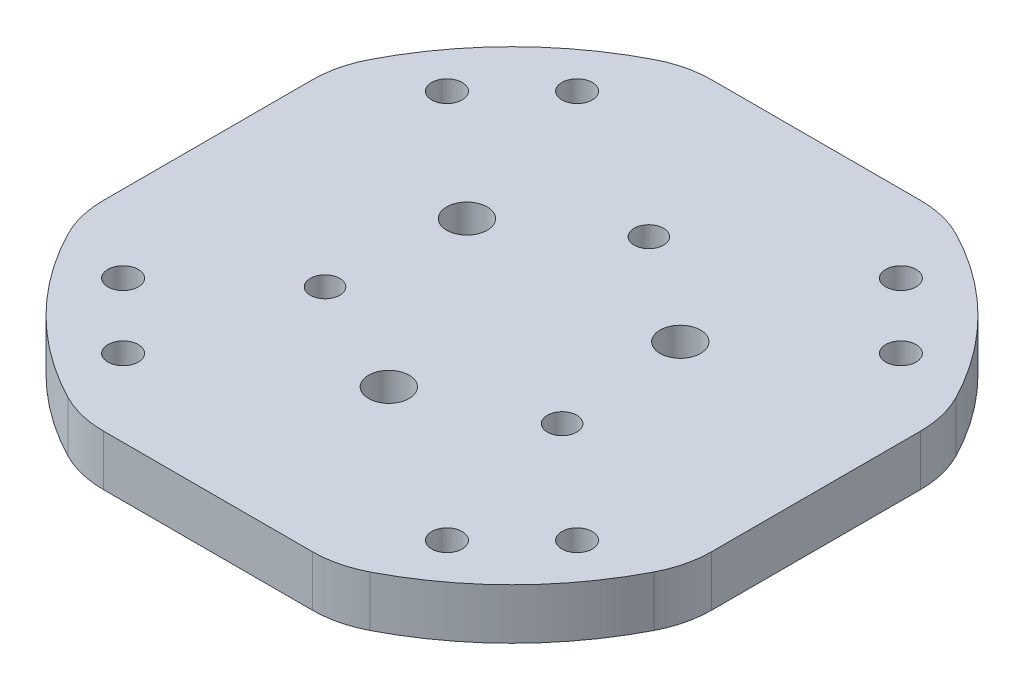
SolidWorks part; units mm, degrees
ref_plane "前视基准面" through (0, 0, 0) normal (0, 0, 1) x (1, 0, 0)
ref_plane "上视基准面" through (0, 0, 0) normal (0, 1, 0) x (1, 0, 0)
ref_plane "右视基准面" through (0, 0, 0) normal (1, 0, 0) x (0, 0, -1)
sketch "草图1" plane through (0, 0, 0) normal (0, 1, 0) x (1, 0, 0)
  line L0 (0, 0) -> (0, 33.3478) construction
  line L1 (0, 0) -> (11.2563, 0) construction
  line L2 (-11.6913, -6.75) -> (0, 0) construction
  line L3 (0, 0) -> (11.6913, -6.75) construction
  line L4 (0, 0) -> (-10.5222, 6.075) construction
  line L5 (10.5222, 6.075) -> (0, 0) construction
  circle A0 centre (0, 0) radius 19
  circle A1 centre (0, 13.5) radius 1.45
  circle A2 centre (0, 0) radius 13.5 construction
  circle A3 centre (-11.6913, -6.75) radius 1.45
  circle A4 centre (11.6913, -6.75) radius 1.45
  circle A5 centre (0, 0) radius 12.15 construction
  circle A6 centre (-10.5222, 6.075) radius 2
  circle A7 centre (0, -12.15) radius 2
  circle A8 centre (10.5222, 6.075) radius 2
  dimension "D1" = 38
  dimension "D2" = 27
  dimension "D3" = 2.9
  dimension "D6" = 24.3
  dimension "D8" = 4
  dimension "D4" = 120
  dimension "D5" = 120
  dimension "D7" = 60
  dimension "D9" = 60
extrude "凸台-拉伸1" add sketch "草图1" along normal blind 12
sketch "草图2" plane through (0, 12, 0) normal (0, 1, 0) x (1, 0, 0)
  line L0 (0, 21.9393) -> (0, 0) construction
  line L1 (0, 21.9393) -> (-19, 10.9697)
  line L2 (-19, 10.9697) -> (-19, -10.9697)
  line L3 (-19, -10.9697) -> (0, -21.9393)
  line L4 (0, -21.9393) -> (19, -10.9697)
  line L5 (19, -10.9697) -> (19, 10.9697)
  line L6 (19, 10.9697) -> (0, 21.9393)
  circle A0 centre (0, 0) radius 19 construction
  circle A1 centre (0, 13.5) radius 1.45
  circle A2 centre (0, 13.5) radius 1.45 construction
  circle A3 centre (-10.5222, 6.075) radius 2
  circle A4 centre (-10.5222, 6.075) radius 2 construction
  circle A5 centre (10.5222, 6.075) radius 2
  circle A6 centre (10.5222, 6.075) radius 2 construction
  circle A7 centre (-11.6913, -6.75) radius 1.45
  circle A8 centre (-11.6913, -6.75) radius 1.45 construction
  circle A9 centre (0, -12.15) radius 2
  circle A10 centre (0, -12.15) radius 2 construction
  circle A11 centre (11.6913, -6.75) radius 1.45
  circle A12 centre (11.6913, -6.75) radius 1.45 construction
  dimension "D1" = 38
extrude "凸台-拉伸2" add sketch "草图2" against normal blind 7
sketch "草图3" plane through (9.5, 0, 16.4545) normal (0.5, 0, 0.866) x (0.866, 0, -0.5)
  line L1 (0, 12) -> (0, 5) construction
  line L2 (-10.9697, 12) -> (10.9697, 12) construction
  circle A1 centre (0, 8.5) radius 1.45
  dimension "D1" = 2.9
extrude "切除-拉伸1" cut sketch "草图3" against normal blind 8
sketch "草图4" plane through (-9.5, 0, 16.4545) normal (-0.5, 0, 0.866) x (0.866, 0, 0.5)
  line L0 (0, 5) -> (0, 12) construction
  line L1 (-10.9697, 12) -> (10.9697, 12) construction
  circle A0 centre (0, 8.5) radius 1.45
  dimension "D1" = 2.9
extrude "切除-拉伸2" cut sketch "草图4" against normal blind 8
sketch "草图5" plane through (-19, 0, 0) normal (-1, 0, 0) x (0, 0, 1)
  line L0 (0, 5) -> (0, 12) construction
  line L1 (-10.9697, 12) -> (10.9697, 12) construction
  circle A0 centre (0, 8.5) radius 1.45
  dimension "D1" = 2.9
extrude "切除-拉伸3" cut sketch "草图5" against normal blind 8
sketch "草图6" plane through (19, 0, 0) normal (1, 0, 0) x (0, 0, -1)
  line L0 (0, 12) -> (0, 5) construction
  line L1 (-10.9697, 12) -> (10.9697, 12) construction
  circle A0 centre (0, 8.5) radius 1.45
  dimension "D1" = 2.9
extrude "切除-拉伸4" cut sketch "草图6" against normal blind 8
sketch "草图7" plane through (9.5, 0, -16.4545) normal (0.5, 0, -0.866) x (-0.866, 0, -0.5)
  line L0 (0, 12) -> (0, 5) construction
  line L1 (-10.9697, 12) -> (10.9697, 12) construction
  circle A0 centre (0, 8.5) radius 1.45
  dimension "D1" = 2.9
extrude "切除-拉伸5" cut sketch "草图7" against normal blind 8
sketch "草图8" plane through (0, 12, 0) normal (0, 1, 0) x (1, 0, 0)
  line L0 (0, 0) -> (0, 38.6602) construction
  line L1 (0, 0) -> (44.9682, 0) construction
  line L2 (0, 0) -> (-22.3882, 15.9693) construction
  line L3 (0, 0) -> (-15.9693, 22.3882) construction
  line L4 (10.3078, 30) -> (-10.3078, 30)
  line L5 (-30, 30) -> (30, 30) construction
  line L6 (-30, 30) -> (-30, -30) construction
  line L7 (-30, -30) -> (30, -30) construction
  line L8 (30, 30) -> (30, -30) construction
  line L9 (-30, 30) -> (30, -30) construction
  line L10 (-30, -30) -> (30, 30) construction
  line L11 (-30, -10.3078) -> (-30, 10.3078)
  line L12 (30, -10.3078) -> (30, 10.3078)
  line L13 (10.3078, -30) -> (-10.3078, -30)
  circle A0 centre (0, 0) radius 32.5 construction
  circle A1 centre (0, 0) radius 27.5 construction
  circle A2 centre (-22.3882, 15.9693) radius 1.5
  circle A3 centre (-15.9693, 22.3882) radius 1.5
  circle A4 centre (-22.3882, -15.9693) radius 1.5
  circle A5 centre (-15.9693, -22.3882) radius 1.5
  circle A6 centre (15.9693, -22.3882) radius 1.5
  circle A7 centre (22.3882, -15.9693) radius 1.5
  circle A8 centre (22.3882, 15.9693) radius 1.5
  circle A9 centre (15.9693, 22.3882) radius 1.5
  arc A10 (-14.889, 28.8889) -> (-28.8889, 14.889) centre (0, 0) ccw
  arc A11 (14.889, 28.8889) -> (28.8889, 14.889) centre (0, 0) cw
  arc A12 (14.889, -28.8889) -> (28.8889, -14.889) centre (0, 0) ccw
  arc A13 (-14.889, -28.8889) -> (-28.8889, -14.889) centre (0, 0) cw
  arc A14 (-10.3078, -30) -> (-14.889, -28.8889) centre (-10.3078, -20) cw
  arc A15 (-28.8889, -14.889) -> (-30, -10.3078) centre (-20, -10.3078) cw
  arc A16 (-30, 10.3078) -> (-28.8889, 14.889) centre (-20, 10.3078) cw
  arc A17 (-14.889, 28.8889) -> (-10.3078, 30) centre (-10.3078, 20) cw
  arc A18 (14.889, 28.8889) -> (10.3078, 30) centre (10.3078, 20) ccw
  arc A19 (28.8889, 14.889) -> (30, 10.3078) centre (20, 10.3078) cw
  arc A20 (28.8889, -14.889) -> (30, -10.3078) centre (20, -10.3078) ccw
  arc A21 (14.889, -28.8889) -> (10.3078, -30) centre (10.3078, -20) cw
  circle A22 centre (0, 13.5) radius 1.5
  circle A23 centre (11.6913, -6.75) radius 1.5
  circle A24 centre (0, -12.15) radius 2
  circle A25 centre (10.5222, 6.075) radius 2
  circle A26 centre (-11.6913, -6.75) radius 1.5
  circle A27 centre (-10.5222, 6.075) radius 2
  circle A28 centre (-10.5222, 6.075) radius 2 construction
  circle A29 centre (10.5222, 6.075) radius 2 construction
  point P34 (0, 30)
  point P37 (30, 0)
  point P40 (-30, 0)
  point P42 (-12.5, -30)
  point P45 (-30, -12.5)
  point P48 (-30, 12.5)
  point P51 (-12.5, 30)
  point P54 (12.5, 30)
  point P57 (30, 12.5)
  point P60 (30, -12.5)
  point P63 (12.5, -30)
  dimension "D1" = 65
  dimension "D2" = 55
  dimension "D5" = 3
  dimension "D7" = 10
  dimension "D8" = 10
  dimension "D9" = 3
  dimension "D3" = 35.5
  dimension "D4" = 35.5
  dimension "D6" = 60
extrude "凸台-拉伸3" add sketch "草图8" against normal blind 5
fillet "圆角1" radius 3 6 edges at (-9.5, 7, 16.4545) (9.5, 7, 16.4545) (19, 7, 0) (9.5, 7, -16.4545) (-9.5, 7, -16.4545) (-19, 7, 0)
